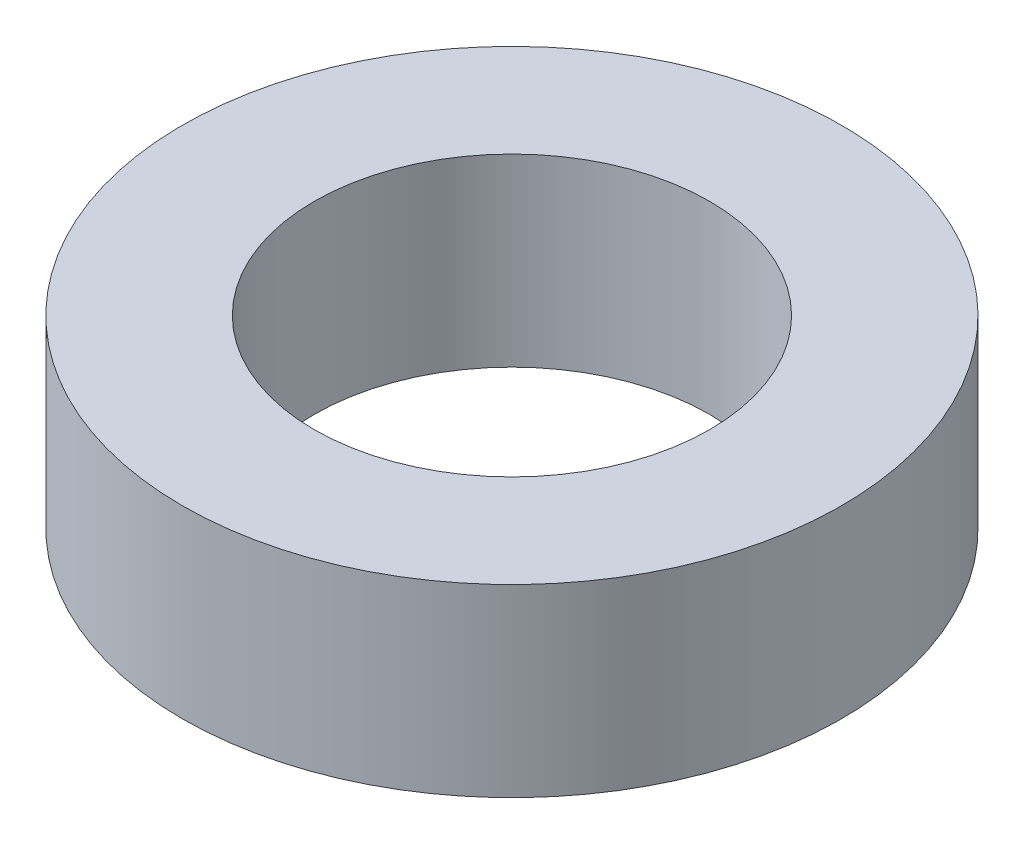
SolidWorks part; units mm, degrees
ref_plane "Front Plane" through (0, 0, 0) normal (0, 0, 1) x (1, 0, 0)
ref_plane "Top Plane" through (0, 0, 0) normal (0, 1, 0) x (1, 0, 0)
ref_plane "Right Plane" through (0, 0, 0) normal (1, 0, 0) x (0, 0, -1)
sketch "Sketch1" plane through (0, 0, 0) normal (0, 1, 0) x (1, 0, 0)
  circle A0 centre (0, 0) radius 50
  dimension "FLANGE_OD" = 100
extrude "Boss-Extrude1" add sketch "Sketch1" along normal blind 28
sketch "Sketch2" plane through (0, 0, 0) normal (0, 1, 0) x (1, 0, 0)
  circle A0 centre (0, 0) radius 30
  dimension "BORE_D" = 60
extrude "Cut-Extrude1" cut sketch "Sketch2" along normal through all
sketch "Sketch3" plane through (0, 28, 0) normal (0, 1, 0) x (1, 0, 0)
  circle A0 centre (0, 0) radius 22.1163 construction
  circle A1 centre (-22.1163, 0) radius 3.0531
  dimension "BOLT_D" = 6.1063
  dimension "BOLT_PCD" = 44.2325
extrude "Cut-Extrude2" cut sketch "Sketch3" against normal blind 16.8226 rebuild error yes
pattern_circular "CirPattern1" count 6 over 360 rebuild error yes
